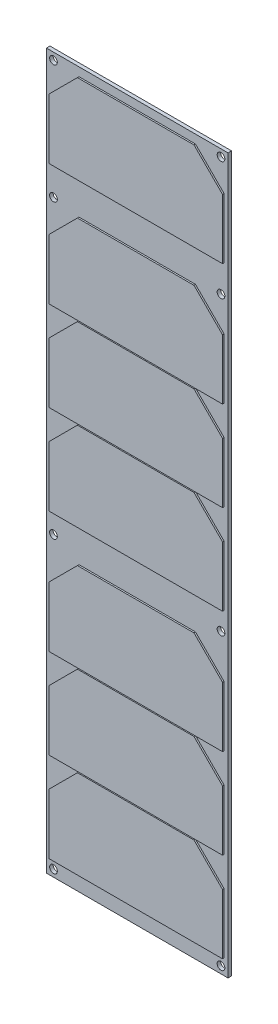
SolidWorks part; units mm, degrees
ref_plane "Front Plane" through (0, 0, 0) normal (0, 0, 1) x (1, 0, 0)
ref_plane "Top Plane" through (0, 0, 0) normal (0, 1, 0) x (1, 0, 0)
ref_plane "Right Plane" through (0, 0, 0) normal (1, 0, 0) x (0, 0, -1)
sketch "Sketch1" plane through (0, 0, 0) normal (0, 0, 1) x (1, 0, 0)
  line L0 (-93.968, 75.9855) -> (-93.968, -249.0145)
  line L1 (-93.968, -249.0145) -> (-11.368, -249.0145)
  line L2 (-11.368, -249.0145) -> (-11.368, 75.9855)
  line L3 (-11.368, 75.9855) -> (-93.968, 75.9855)
  line L40 (-92.168, -214.7145) -> (-79.168, -201.7145)
  line L41 (-79.168, -201.7145) -> (-26.168, -201.7145)
  line L42 (-26.168, -201.7145) -> (-13.168, -214.7145)
  line L43 (-13.168, -214.7145) -> (-13.168, -242.0145)
  line L44 (-13.168, -242.0145) -> (-92.168, -242.0145)
  line L45 (-92.168, -242.0145) -> (-92.168, -214.7145)
  line L46 (-92.168, -173.9145) -> (-79.168, -160.9145)
  line L47 (-79.168, -160.9145) -> (-26.168, -160.9145)
  line L48 (-26.168, -160.9145) -> (-13.168, -173.9145)
  line L49 (-13.168, -173.9145) -> (-13.168, -201.2145)
  line L50 (-13.168, -201.2145) -> (-92.168, -201.2145)
  line L51 (-92.168, -201.2145) -> (-92.168, -173.9145)
  line L52 (-92.168, -37.0145) -> (-79.168, -24.0145)
  line L53 (-79.168, -24.0145) -> (-26.168, -24.0145)
  line L54 (-26.168, -24.0145) -> (-13.168, -37.0145)
  line L55 (-92.168, -133.1145) -> (-79.168, -120.1145)
  line L56 (-79.168, -120.1145) -> (-26.168, -120.1145)
  line L57 (-26.168, -120.1145) -> (-13.168, -133.1145)
  line L58 (-13.168, -133.1145) -> (-13.168, -160.4145)
  line L59 (-13.168, -160.4145) -> (-92.168, -160.4145)
  line L60 (-92.168, -160.4145) -> (-92.168, -133.1145)
  line L67 (-92.168, -77.8145) -> (-79.168, -64.8145)
  line L68 (-79.168, -64.8145) -> (-26.168, -64.8145)
  line L69 (-26.168, -64.8145) -> (-13.168, -77.8145)
  line L70 (-13.168, -77.8145) -> (-13.168, -105.1145)
  line L71 (-13.168, -105.1145) -> (-92.168, -105.1145)
  line L72 (-92.168, -105.1145) -> (-92.168, -77.8145)
  line L73 (-13.168, -37.0145) -> (-13.168, -64.3145)
  line L74 (-13.168, -64.3145) -> (-92.168, -64.3145)
  line L75 (-92.168, -64.3145) -> (-92.168, -37.0145)
  line L76 (-92.168, 3.7855) -> (-79.168, 16.7855)
  line L77 (-79.168, 16.7855) -> (-26.168, 16.7855)
  line L78 (-26.168, 16.7855) -> (-13.168, 3.7855)
  line L79 (-13.168, 3.7855) -> (-13.168, -23.5145)
  line L80 (-13.168, -23.5145) -> (-92.168, -23.5145)
  line L81 (-92.168, -23.5145) -> (-92.168, 3.7855)
  line L82 (-92.168, 59.0855) -> (-79.168, 72.0855)
  line L83 (-79.168, 72.0855) -> (-26.168, 72.0855)
  line L84 (-26.168, 72.0855) -> (-13.168, 59.0855)
  line L85 (-13.168, 59.0855) -> (-13.168, 31.7855)
  line L86 (-13.168, 31.7855) -> (-92.168, 31.7855)
  line L87 (-92.168, 31.7855) -> (-92.168, 59.0855)
  circle A0 centre (-90.768, 72.7855) radius 1.75
  circle A1 centre (-14.568, 72.7855) radius 1.75
  circle A2 centre (-14.568, -245.8145) radius 1.75
  circle A3 centre (-90.768, -245.8145) radius 1.75
  circle A4 centre (-90.768, -114.0145) radius 1.75
  circle A5 centre (-14.568, -114.0145) radius 1.75
  circle A6 centre (-90.768, 18.7855) radius 1.75
  circle A7 centre (-14.568, 18.7855) radius 1.75
  dimension "D3" = 3.5
  dimension "D4" = 3.5
  dimension "D5" = 3.5
  dimension "D6" = 3.5
  dimension "D7" = 3.5
  dimension "D8" = 3.5
  dimension "D9" = 3.5
  dimension "D10" = 3.5
  dimension "D1" = 82.6
  dimension "D2" = 325
  dimension "D11" = 3.2
  dimension "D12" = 3.2
  dimension "D13" = 3.2
  dimension "D14" = 3.2
  dimension "D15" = 3.2
  dimension "D16" = 57.2
  dimension "D17" = 3.2
  dimension "D18" = 57.2
  dimension "D19" = 3.2
  dimension "D20" = 3.2
  dimension "D21" = 190
  dimension "D22" = 190
  dimension "D23" = 3.2
  dimension "D24" = 3.2
  dimension "D25" = 321.8
  dimension "D26" = 321.8
  dimension "D27" = 1.8
  dimension "D28" = 1.8
  dimension "D29" = 53
  dimension "D30" = 13
  dimension "D31" = 27.3
  dimension "D32" = 27.3
  dimension "D33" = 7
  dimension "D34" = 79
  dimension "D35" = 53
  dimension "D36" = 27.3
  dimension "D37" = 13
  dimension "D38" = 1.8
  dimension "D39" = 0.5
  dimension "D40" = 79
  dimension "D41" = 27.3
  dimension "D42" = 13
  dimension "D43" = 53
  dimension "D44" = 1.8
  dimension "D45" = 0.5
  dimension "D46" = 79
  dimension "D47" = 27.3
  dimension "D48" = 13
  dimension "D49" = 53
  dimension "D50" = 27.3
  dimension "D51" = 27.3
  dimension "D52" = 15
  dimension "D53" = 27.3
  dimension "D54" = 1.8
  dimension "D55" = 79
  dimension "D56" = 27.3
  dimension "D57" = 13
  dimension "D58" = 53
  dimension "D59" = 27.3
  dimension "D60" = 1.8
  dimension "D61" = 0.5
  dimension "D62" = 79
  dimension "D63" = 27.3
  dimension "D64" = 13
  dimension "D65" = 53
  dimension "D66" = 27.3
  dimension "D67" = 1.8
  dimension "D68" = 0.5
  dimension "D69" = 15
  dimension "D70" = 79
  dimension "D71" = 1.8
  dimension "D72" = 27.3
  dimension "D73" = 13
  dimension "D74" = 53
  dimension "D75" = 27.3
extrude "Boss-Extrude4" add sketch "Sketch1" along normal blind 1.6
extrude "Boss-Extrude5" add sketch "Sketch1<8>" along normal blind 2.3 contours L87 L86 L85 L84 L83 L82 | L81 L80 L79 L78 L77 L76 | L75 L74 L73 L54 L53 L52 | L72 L71 L70 L69 L68 L67 | L60 L59 L58 L57 L56 L55 | L51 L50 L49 L48 L47 L46 | L45 L44 L43 L42 L41 L40 region at (-52.668, -222.7511, 0) region at (-52.668, -181.9511, 0) region at (-52.668, -45.0511, 0) region at (-52.668, -141.1511, 0) region at (-52.668, -85.8511, 0) region at (-52.668, -4.2511, 0) region at (-52.668, 51.0489, 0)
sketch "Sketch1<8>" plane through (0, 0, 0) normal (0, 0, 1) x (1, 0, 0) same geometry as "Sketch1"
